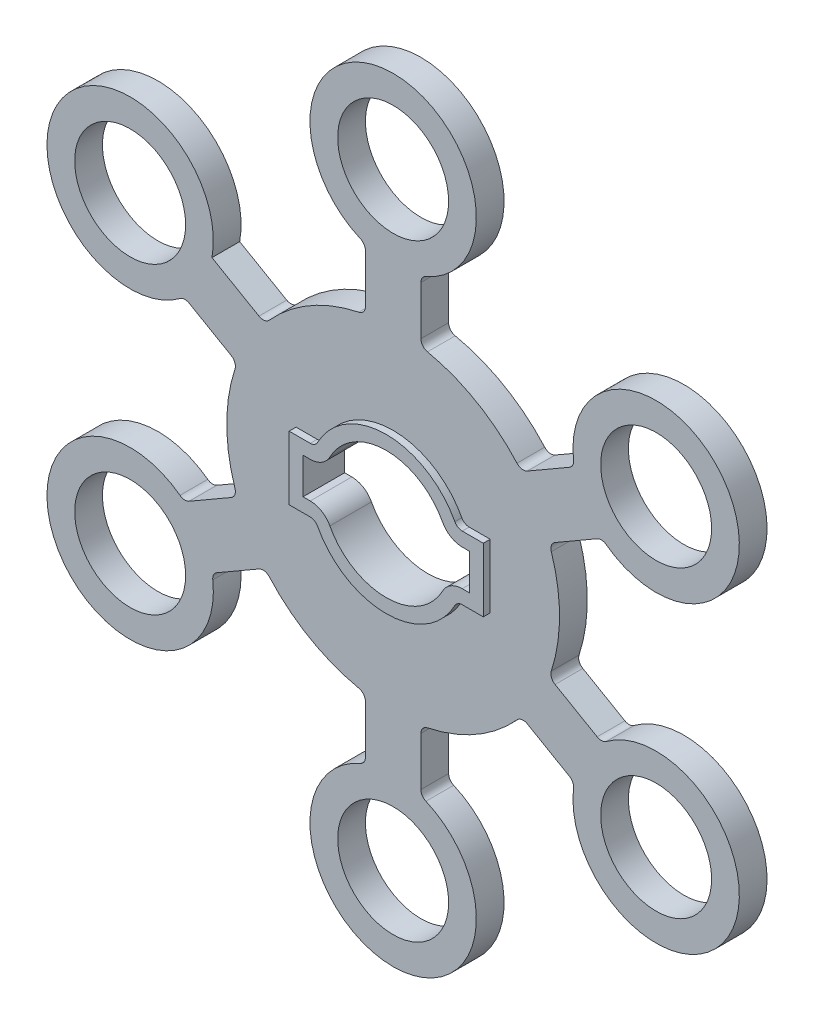
SolidWorks part; units mm, degrees
ref_plane "Front Plane" through (0, 0, 0) normal (0, 0, 1) x (1, 0, 0)
ref_plane "Top Plane" through (0, 0, 0) normal (0, 1, 0) x (1, 0, 0)
ref_plane "Right Plane" through (0, 0, 0) normal (1, 0, 0) x (0, 0, -1)
sketch "Sketch1" plane through (0, 0, 0) normal (0, 0, 1) x (1, 0, 0)
  line L0 (0, 0) -> (0, 58209.2678) construction
  line L1 (0, 0) -> (58209.2678, 0) construction
  line L2 (0, 0) -> (94.8298, 54.75) construction
  line L3 (48.3854, 39.4823) -> (63.5619, 48.2445)
  line L4 (58.3854, 22.1618) -> (73.5619, 30.924)
  line L5 (58.3854, -22.1618) -> (73.5619, -30.924)
  line L6 (48.3854, -39.4823) -> (63.5619, -48.2445)
  line L7 (10, -61.6441) -> (10, -79.1685)
  line L8 (-10, -61.6441) -> (-10, -79.1685)
  line L9 (-48.3854, -39.4823) -> (-63.5619, -48.2445)
  line L10 (-58.3854, -22.1618) -> (-73.5619, -30.924)
  line L11 (-58.3854, 22.1618) -> (-73.5619, 30.924)
  line L12 (-48.3854, 39.4823) -> (-65.3349, 49.2681)
  line L13 (-10, 61.6441) -> (-10, 79.1685)
  line L14 (10, 61.6441) -> (10, 79.1685)
  line L15 (-27.3998, 11.5) -> (-35, 11.5)
  line L16 (-35, 11.5) -> (-35, -11.5)
  line L17 (-35, -11.5) -> (-27.3998, -11.5)
  line L18 (35, -11.5) -> (27.3998, -11.5)
  line L19 (27.3998, 11.5) -> (35, 11.5)
  line L20 (35, 11.5) -> (35, -11.5)
  line L21 (-27.3998, 6.5) -> (-30, 6.5)
  line L22 (-30, 6.5) -> (-30, -6.5)
  line L23 (-30, -6.5) -> (-27.3998, -6.5)
  line L24 (30, -6.5) -> (27.3998, -6.5)
  line L25 (30, 6.5) -> (30, -6.5)
  line L26 (27.3998, 6.5) -> (30, 6.5)
  arc A0 (-24.7482, -13.0968) -> (24.7482, -13.0968) centre (0, 0) ccw
  arc A1 (-57.0337, 18.6321) -> (-57.0337, -18.6321) centre (0, 0) ccw
  circle A2 centre (0, 0) radius 109.5 construction
  circle A3 centre (94.8298, 54.75) radius 20
  arc A4 (76.859, 30.7281) -> (65.0408, 51.1978) centre (94.8298, 54.75) ccw
  circle A5 centre (94.8298, -54.75) radius 20
  arc A6 (65.0408, -51.1978) -> (76.859, -30.7281) centre (94.8298, -54.75) ccw
  circle A7 centre (0, -109.5) radius 20
  arc A8 (-11.8182, -81.9259) -> (11.8182, -81.9259) centre (0, -109.5) ccw
  circle A9 centre (-94.8298, -54.75) radius 20
  arc A10 (-76.859, -30.7281) -> (-65.0408, -51.1978) centre (-94.8298, -54.75) ccw
  circle A11 centre (-94.8298, 54.75) radius 20
  arc A12 (-65.3349, 49.2681) -> (-76.859, 30.7281) centre (-94.8298, 54.75) ccw
  circle A13 centre (0, 109.5) radius 20
  arc A14 (11.8182, 81.9259) -> (-11.8182, 81.9259) centre (0, 109.5) ccw
  arc A15 (-12.381, 58.7087) -> (-44.6528, 40.0766) centre (0, 0) ccw
  arc A16 (44.6528, 40.0766) -> (12.381, 58.7087) centre (0, 0) ccw
  arc A17 (57.0337, -18.6321) -> (57.0337, 18.6321) centre (0, 0) ccw
  arc A18 (12.381, -58.7087) -> (44.6528, -40.0766) centre (0, 0) ccw
  arc A19 (-44.6528, -40.0766) -> (-12.381, -58.7087) centre (0, 0) ccw
  arc A20 (24.7482, 13.0968) -> (-24.7482, 13.0968) centre (0, 0) ccw
  arc A21 (27.3998, 11.5) -> (24.7482, 13.0968) centre (27.3998, 14.5) cw
  arc A22 (27.3998, -11.5) -> (24.7482, -13.0968) centre (27.3998, -14.5) ccw
  arc A23 (-27.3998, -11.5) -> (-24.7482, -13.0968) centre (-27.3998, -14.5) cw
  arc A24 (10, 79.1685) -> (11.8182, 81.9259) centre (13, 79.1685) cw
  arc A25 (10, 61.6441) -> (12.381, 58.7087) centre (13, 61.6441) ccw
  arc A26 (-10, 79.1685) -> (-11.8182, 81.9259) centre (-13, 79.1685) ccw
  arc A27 (-10, 61.6441) -> (-12.381, 58.7087) centre (-13, 61.6441) cw
  arc A28 (-48.3854, 39.4823) -> (-44.6528, 40.0766) centre (-46.8854, 42.0804) ccw
  arc A29 (-73.5619, 30.924) -> (-76.859, 30.7281) centre (-75.0619, 28.3259) ccw
  arc A30 (-58.3854, 22.1618) -> (-57.0337, 18.6321) centre (-59.8854, 19.5637) cw
  arc A31 (-73.5619, -30.924) -> (-76.859, -30.7281) centre (-75.0619, -28.3259) cw
  arc A32 (-58.3854, -22.1618) -> (-57.0337, -18.6321) centre (-59.8854, -19.5637) ccw
  arc A33 (-63.5619, -48.2445) -> (-65.0408, -51.1978) centre (-62.0619, -50.8426) ccw
  arc A34 (-48.3854, -39.4823) -> (-44.6528, -40.0766) centre (-46.8854, -42.0804) cw
  arc A35 (-10, -79.1685) -> (-11.8182, -81.9259) centre (-13, -79.1685) cw
  arc A36 (-10, -61.6441) -> (-12.381, -58.7087) centre (-13, -61.6441) ccw
  arc A37 (10, -79.1685) -> (11.8182, -81.9259) centre (13, -79.1685) ccw
  arc A38 (10, -61.6441) -> (12.381, -58.7087) centre (13, -61.6441) cw
  arc A39 (63.5619, -48.2445) -> (65.0408, -51.1978) centre (62.0619, -50.8426) cw
  arc A40 (48.3854, -39.4823) -> (44.6528, -40.0766) centre (46.8854, -42.0804) ccw
  arc A41 (73.5619, -30.924) -> (76.859, -30.7281) centre (75.0619, -28.3259) ccw
  arc A42 (58.3854, -22.1618) -> (57.0337, -18.6321) centre (59.8854, -19.5637) cw
  arc A43 (-27.3998, 11.5) -> (-24.7482, 13.0968) centre (-27.3998, 14.5) ccw
  arc A44 (73.5619, 30.924) -> (76.859, 30.7281) centre (75.0619, 28.3259) cw
  arc A45 (58.3854, 22.1618) -> (57.0337, 18.6321) centre (59.8854, 19.5637) ccw
  arc A46 (63.5619, 48.2445) -> (65.0408, 51.1978) centre (62.0619, 50.8426) ccw
  arc A47 (48.3854, 39.4823) -> (44.6528, 40.0766) centre (46.8854, 42.0804) cw
  arc A48 (20.3289, 10.7581) -> (-20.3289, 10.7581) centre (0, 0) ccw
  arc A49 (-27.3998, 6.5) -> (-20.3289, 10.7581) centre (-27.3998, 14.5) ccw
  arc A50 (-27.3998, -6.5) -> (-20.3289, -10.7581) centre (-27.3998, -14.5) cw
  arc A51 (-20.3289, -10.7581) -> (20.3289, -10.7581) centre (0, 0) ccw
  arc A52 (27.3998, -6.5) -> (20.3289, -10.7581) centre (27.3998, -14.5) ccw
  arc A53 (27.3998, 6.5) -> (20.3289, 10.7581) centre (27.3998, 14.5) cw
  point P11 (25.5294, 11.5)
  point P42 (25.5294, -11.5)
  point P54 (0, 0)
  point P60 (-25.5294, -11.5)
  point P101 (-25.5294, 11.5)
  point P110 (46.2348, 38.2407)
  dimension "D1" = 56
  dimension "D2" = 120
  dimension "D3" = 219
  dimension "D4" = 40
  dimension "D5" = 60
  dimension "D11" = 3
  dimension "D6" = 30
  dimension "D7" = 20
  dimension "D8" = 6
  dimension "D9" = 35
  dimension "D10" = 23
  dimension "D12" = 5
extrude "Boss-Extrude1" add sketch "Sketch1" along normal mid plane 15 contours A43 L15 L16 L17 A23 A0 A22 L18 L20 L19 A21 A20 A53 L26 L25 L24 A52 A51 A50 L23 L22 L21 A49 A48 region at (-25.3897, 11.1621, 0)
extrude "Boss-Extrude2" add sketch "Sketch1<3>" along normal mid plane 10 contours L3 A47 A16 A25 L14 A24 A14 A26 L13 A27 A15 A28 L12 A12 A29 L11 A30 A1 A32 L10 A31 A10 A33 L9 A34 A19 A36 L8 A35 A8 A37 L7 A38 A18 A40 L6 A39 A6 A41 L5 A42 A17 A45 L4 A44 A4 A46 L15 A43 A20 region at (57.8456, 40.6211, 0)
sketch "Sketch1<3>" plane through (0, 0, 0) normal (0, 0, 1) x (1, 0, 0) same geometry as "Sketch1"
